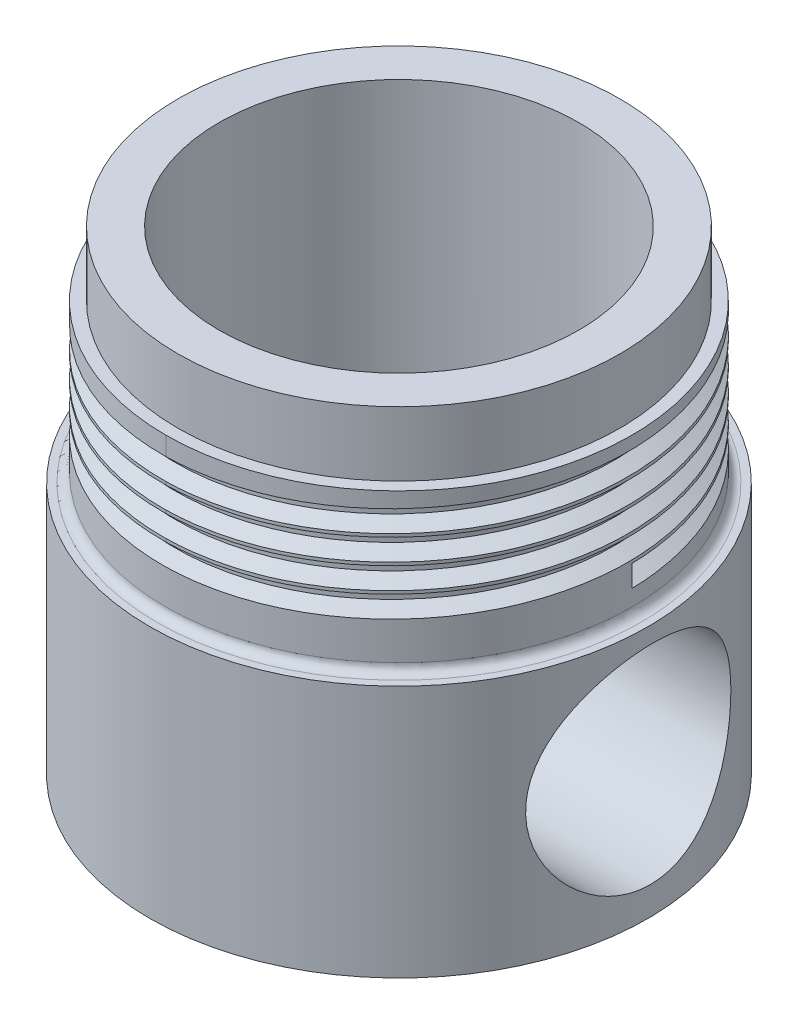
SolidWorks part; units mm, degrees
ref_plane "Front Plane" through (0, 0, 0) normal (0, 0, 1) x (1, 0, 0)
ref_plane "Top Plane" through (0, 0, 0) normal (0, 1, 0) x (1, 0, 0)
ref_plane "Right Plane" through (0, 0, 0) normal (1, 0, 0) x (0, 0, -1)
sketch "Sketch1" plane through (0, 0, 0) normal (0, 1, 0) x (1, 0, 0)
  circle A0 centre (0, 0) radius 14.2494
  dimension "D1" = 28.4988
extrude "Boss-Extrude1" add sketch "Sketch1" along normal blind 27.1526
sketch "Sketch2" plane through (0, 27.1526, 0) normal (0, 1, 0) x (1, 0, 0)
  circle A0 centre (0, 0) radius 14.2494
  circle A1 centre (0, 0) radius 13.3223
  circle M3 centre (0, 0) radius 14.2494
  dimension "D1" = 26.6446
extrude "Cut-Extrude1" cut sketch "Sketch2" against normal blind 12.7 contours A1 M3 region at (-13.8464, 27.1526, 0)
sketch "Sketch3" plane through (0, 27.1526, 0) normal (0, 1, 0) x (1, 0, 0)
  circle A0 centre (0, 0) radius 10.287
  dimension "D1" = 20.574
extrude "Cut-Extrude2" cut sketch "Sketch3" against normal blind 18.923
sketch "Sketch4" plane through (0, 8.2296, 0) normal (0, 1, 0) x (1, 0, 0)
  circle A0 centre (0, 0) radius 1.524
  dimension "D1" = 3.048
thread "Thread1" pitch 1.4111 method cut profile "Thread Profile1" start angle 0, offset 3.683, length 6.35, pitch 1.4111, diameter 26.6446
ref_plane "Plane1" through (-13.3223, 23.4696, 0) normal (0, 0, 1) x (-1, 0, 0)
sketch "Thread Profile1" plane through (-13.3223, 23.4696, 0) normal (0, 0, 1) x (-1, 0, 0)
  line L0 (0, 0) -> (0, 1.4111) construction
  line L11 (0, 0) -> (0, 1.2347)
  line L12 (0, 1.2347) -> (-0.7638, 0.7937)
  line L13 (-0.7638, 0.7937) -> (-0.7638, 0.441)
  line L15 (-0.7638, 0.441) -> (0, 0)
  line L17 (-0.7638, 0.6174) -> (0, 0.6174) construction
  point P2 (0, 0)
  dimension "Pitch" = 1.4111
  dimension "Profile_Angle" = 60
  dimension "Profile_Land" = 0.3528
  dimension "Profile_Height" = 0.7638
sketch "Sketch7" plane through (0, 27.1526, 0) normal (0, 1, 0) x (1, 0, 0)
  circle A0 centre (0, 0) radius 13.3223
  circle A1 centre (0, 0) radius 12.6365
  circle M3 centre (0, 0) radius 13.3223
  dimension "D1" = 25.273
extrude "Cut-Extrude4" cut sketch "Sketch7" against normal blind 3.683 contours A1 M3 region at (-12.9455, 27.1526, 0)
fillet "Fillet2" radius 0.508 1 edges at (0, 14.4526, 13.3223)
hole_wizard "1/4-18 NPSM Tapped Hole1" positions "3DSketch1" profile "Sketch11" tap size "1/4-18 NPSM" standard "ANSI Inch"
sketch3d "3DSketch1"
  circle A0 centre (0, 0, 0) radius 14.2494 construction
  point P0 (14.2483, 7.5564, -0.1794)
  point P5 (0, 14.2494, 0)
  dimension "D1" = 16.129
sketch "Sketch11" plane through (14.2483, 7.5564, -0.1794) normal (0, 1, 0) x (-0.0126, 0, -0.9999)
  line L0 (0, 0) -> (0, 22.6213)
  line L1 (0, 22.6213) -> (5.9436, 19.05)
  line L2 (5.9436, 19.05) -> (5.9436, 0)
  line L5 (5.9436, 0) -> (0, 0)
  line L10 (0, 22.6213) -> (-5.9436, 19.05) construction
  line L11 (0, -6.35) -> (0, 107.95) construction
  dimension "Tap Drill Dia." = 11.8872
  dimension "Tap Drill Depth" = 19.05
  dimension "Drill Angle" = 118
cosmetic thread "Hole Thread1" parameters "D1"=19.05, "D2"=13.3604
